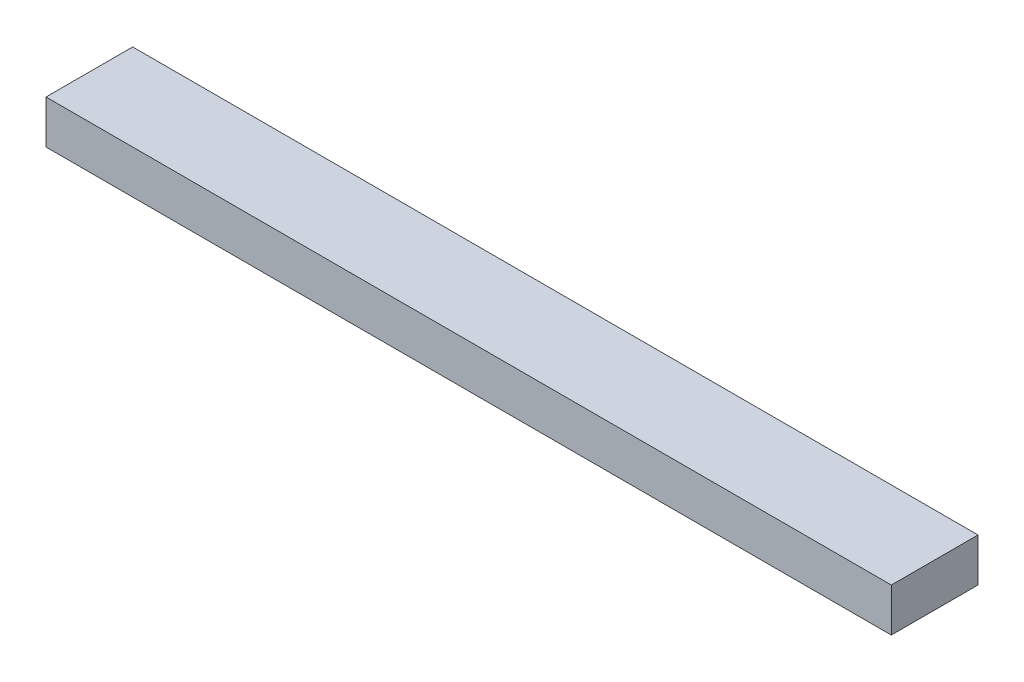
SolidWorks part; units mm, degrees
material "1023 Carbon Steel Sheet (SS)"
ref_plane "Front Plane" through (0, 0, 0) normal (0, 0, 1) x (1, 0, 0)
ref_plane "Top Plane" through (0, 0, 0) normal (0, 1, 0) x (1, 0, 0)
ref_plane "Right Plane" through (0, 0, 0) normal (1, 0, 0) x (0, 0, -1)
sketch "Sketch1" plane through (0, 0, 0) normal (1, 0, 0) x (0, 0, -1)
  line L1 (0, 0) -> (101.6, 0)
  line L2 (0, 0) -> (0, 50.8)
  line L3 (0, 50.8) -> (101.6, 50.8)
  line L4 (101.6, 0) -> (101.6, 50.8)
  dimension "D1" = 50.8
  dimension "D2" = 101.6
extrude "Boss-Extrude1" add sketch "Sketch1" along normal blind 990.6
